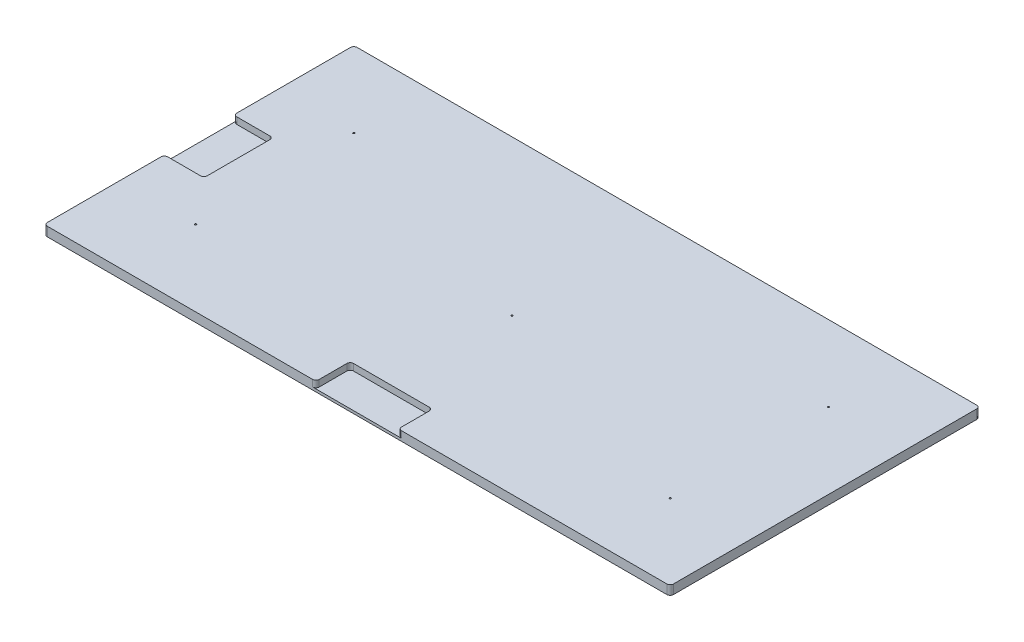
SolidWorks part; units mm, degrees
ref_plane "Front Plane" through (0, 0, 0) normal (0, 0, 1) x (1, 0, 0)
ref_plane "Top Plane" through (0, 0, 0) normal (0, 1, 0) x (1, 0, 0)
ref_plane "Right Plane" through (0, 0, 0) normal (1, 0, 0) x (0, 0, -1)
sketch "Sketch1" plane through (0, 0, 0) normal (0, 1, 0) x (1, 0, 0)
  line L1 (-603.25, -298.45) -> (603.25, -298.45)
  line L2 (-603.25, -298.45) -> (-603.25, 298.45)
  line L3 (-603.25, 298.45) -> (603.25, 298.45)
  line L4 (603.25, -298.45) -> (603.25, 298.45)
  line L5 (-603.25, -298.45) -> (603.25, 298.45) construction
  line L6 (-603.25, 298.45) -> (603.25, -298.45) construction
  point P0 (0, 0)
  dimension "D1" = 1206.5
  dimension "D2" = 596.9
extrude "Boss-Extrude1" add sketch "Sketch1" along normal blind 17.78
hole_wizard "1/8 (0.125) Diameter Hole1" positions "Sketch2" profile "Sketch3" hole size "1/8" standard "ANSI Inch" end condition through all
sketch "Sketch2" plane through (0, 17.78, 0) normal (0, 1, 0) x (1, 0, 0)
  line L1 (-457.2, -152.4) -> (457.2, -152.4) construction
  line L2 (-457.2, -152.4) -> (-457.2, 152.4) construction
  line L3 (-457.2, 152.4) -> (457.2, 152.4) construction
  line L4 (457.2, -152.4) -> (457.2, 152.4) construction
  line L5 (-457.2, -152.4) -> (457.2, 152.4) construction
  line L6 (-457.2, 152.4) -> (457.2, -152.4) construction
  point P0 (0, 0)
  point P1 (457.2, 152.4)
  point P50 (-457.2, -152.4)
  point P51 (-457.2, 152.4)
  point P52 (457.2, -152.4)
  point P63 (0, 0)
  dimension "D1" = 914.4
  dimension "D2" = 304.8
sketch "Sketch3" plane through (0, 17.78, 0) normal (1, 0, 0) x (0, 0, 1)
  line L0 (0, 0) -> (0, 17.78)
  line L1 (0, 17.78) -> (1.5875, 17.78)
  line L2 (1.5875, 17.78) -> (1.5875, 0)
  line L5 (1.5875, 0) -> (0, 0)
  line L11 (0, -6.35) -> (0, 107.95) construction
  dimension "Thru Hole Dia." = 3.175
  dimension "Thru Hole Depth" = 17.78
fillet "Fillet1" radius 6.35 4 edges at (603.25, 8.89, -298.45) (603.25, 8.89, 298.45) (-603.25, 8.89, 298.45) (-603.25, 8.89, -298.45)
sketch "Sketch4" plane through (0, 17.78, 0) normal (0, 1, 0) x (1, 0, 0)
  line L0 (0, 298.45) -> (0, -298.45) construction
  line L1 (596.9, 298.45) -> (-596.9, 298.45) construction
  line L2 (-596.9, -298.45) -> (596.9, -298.45) construction
  line L3 (-603.25, 0) -> (603.25, 0) construction
  line L4 (-79.375, -232.41) -> (79.375, -232.41)
  line L5 (-79.375, -232.41) -> (-79.375, -298.45)
  line L6 (-79.375, -298.45) -> (79.375, -298.45)
  line L7 (79.375, -232.41) -> (79.375, -298.45)
  line L8 (-79.375, -232.41) -> (79.375, -298.45) construction
  line L9 (-79.375, -298.45) -> (79.375, -232.41) construction
  line L10 (-603.25, 292.1) -> (-603.25, -292.1) construction
  line L11 (603.25, -292.1) -> (603.25, 292.1) construction
  line L13 (-527.05, 66.675) -> (-603.25, 66.675)
  line L14 (-527.05, 66.675) -> (-527.05, -66.675)
  line L15 (-527.05, -66.675) -> (-603.25, -66.675)
  line L16 (-603.25, 66.675) -> (-603.25, -66.675)
  line L17 (-527.05, 66.675) -> (-603.25, -66.675) construction
  line L18 (-527.05, -66.675) -> (-603.25, 66.675) construction
  point P6 (0, -265.43)
  point P17 (-565.15, 0)
  dimension "D1" = 158.75
  dimension "D2" = 66.04
  dimension "D3" = 133.35
  dimension "D4" = 76.2
extrude "Cut-Extrude1" cut sketch "Sketch4" against normal blind 12.7
fillet "Fillet2" radius 6.35 8 edges at (79.375, 11.43, 298.45) (-79.375, 11.43, 298.45) (-79.375, 11.43, 232.41) (79.375, 11.43, 232.41) (-603.25, 11.43, 66.675) (-603.25, 11.43, -66.675) (-527.05, 11.43, 66.675) (-527.05, 11.43, -66.675)
